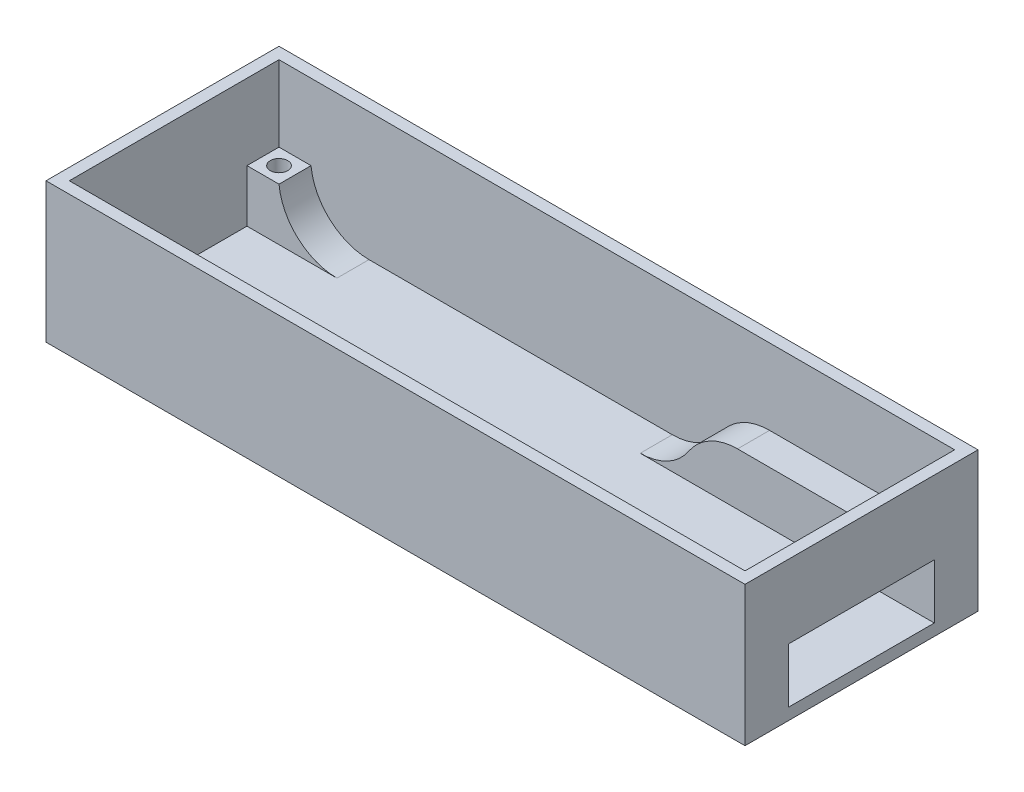
SolidWorks part; units mm, degrees
ref_plane "Front Plane" through (0, 0, 0) normal (0, 0, 1) x (1, 0, 0)
ref_plane "Top Plane" through (0, 0, 0) normal (0, 1, 0) x (1, 0, 0)
ref_plane "Right Plane" through (0, 0, 0) normal (1, 0, 0) x (0, 0, -1)
sketch "Sketch1" plane through (0, 0, 0) normal (0, 1, 0) x (1, 0, 0)
  line L0 (-30, 0) -> (30, 0) construction
  line L1 (-30, -10) -> (30, -10)
  line L2 (-30, -10) -> (-30, 10)
  line L3 (-30, 10) -> (30, 10)
  line L4 (30, -10) -> (30, 10)
  line L5 (0, 10) -> (0, -10) construction
  point P6 (0, 0)
  dimension "D1" = 20
  dimension "D2" = 60
extrude "Boss-Extrude1" add sketch "Sketch1" along normal blind 12
shell "Shell1" thickness 1 removed face at (0, 12, 0)
sketch "Sketch2" plane through (30, 0, 0) normal (1, 0, 0) x (0, 0, -1)
  line L2 (6.25, 5.7) -> (6.25, 1)
  line L3 (-9, 1) -> (9, 1) construction
  line L4 (6.25, 1) -> (-6.25, 1)
  line L5 (0, 1) -> (0, 5.7) construction
  line L6 (-6.25, 5.7) -> (-6.25, 1)
  line L7 (-6.25, 1) -> (-6.25, 5.7) construction
  line L8 (-6.25, 5.7) -> (6.25, 5.7) construction
  line L9 (-6.25, 5.7) -> (6.25, 5.7)
extrude "Cut-Extrude1" cut sketch "Sketch2" against normal blind 12
sketch "Sketch3" plane through (0, 1, 0) normal (0, 1, 0) x (1, 0, 0)
  line L0 (-29, 0) -> (29, 0) construction
  line L1 (-29, 9) -> (-29, -9) construction
  line L2 (29, -9) -> (29, 9) construction
  line L3 (29, 6.25) -> (30, 6.25) construction
  line L4 (29, 9) -> (9.7327, 9)
  line L5 (29, 9) -> (29, 6.25)
  line L6 (29, 6.25) -> (9.7327, 6.25)
  line L7 (9.7327, 9) -> (9.7327, 6.25)
  line L8 (-29, 9) -> (-26.25, 6.25) construction
  line L9 (-29, 9) -> (-26.25, 9)
  line L10 (-29, 9) -> (-29, 6.25)
  line L11 (-29, 6.25) -> (-26.25, 6.25)
  line L12 (-26.25, 9) -> (-26.25, 6.25)
  line L13 (29, 7.625) -> (26.5, 7.625) construction
  line L14 (29, -7.625) -> (26.5, -7.625) construction
  line L15 (-29, -9) -> (-26.25, -6.25) construction
  line L16 (-26.25, -9) -> (-26.25, -6.25)
  line L17 (-29, -6.25) -> (-26.25, -6.25)
  line L18 (-29, -9) -> (-29, -6.25)
  line L19 (-29, -9) -> (-26.25, -9)
  line L20 (9.7327, -9) -> (9.7327, -6.25)
  line L21 (29, -6.25) -> (9.7327, -6.25)
  line L22 (29, -9) -> (29, -6.25)
  line L23 (29, -9) -> (9.7327, -9)
  circle A0 centre (26.5, 7.625) radius 0.75
  circle A1 centre (-27.625, 7.625) radius 0.75
  circle A2 centre (26.5, -7.625) radius 0.75
  circle A3 centre (-27.625, -7.625) radius 0.75
  dimension "D1" = 2.75
extrude "Boss-Extrude2" add sketch "Sketch3" along normal blind 4.5
fillet "Fillet1" radius 5 4 edges at (-26.25, 1, 7.625) (-26.25, 1, -7.625) (9.7327, 1, 7.625) (9.7327, 1, -7.625)
fillet "Fillet2" radius 5 2 edges at (9.7327, 5.5, 7.625) (9.7327, 5.5, -7.625)
